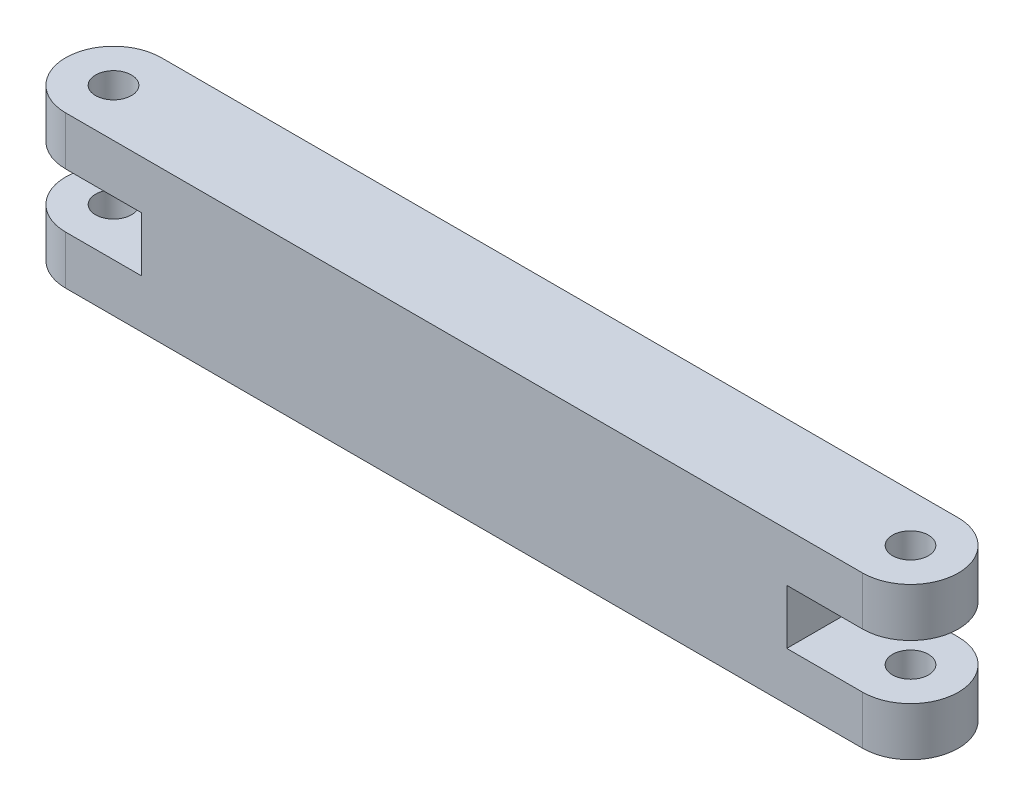
SolidWorks part; units mm, degrees
ref_plane "Front Plane" through (0, 0, 0) normal (0, 0, 1) x (1, 0, 0)
ref_plane "Top Plane" through (0, 0, 0) normal (0, 1, 0) x (1, 0, 0)
ref_plane "Right Plane" through (0, 0, 0) normal (1, 0, 0) x (0, 0, -1)
sketch "Sketch1" plane through (0, 0, 0) normal (0, 1, 0) x (1, 0, 0)
  line L0 (0, 0) -> (0, 17432.9303) construction
  line L1 (0, 0) -> (17432.9303, 0) construction
  line L2 (0, 6) -> (100, 6)
  line L3 (0, -6) -> (100, -6)
  circle A0 centre (0, 0) radius 2.25
  circle A1 centre (100, 0) radius 2.25
  arc A2 (0, 6) -> (0, -6) centre (0, 0) ccw
  arc A3 (100, -6) -> (100, 6) centre (100, 0) ccw
  dimension "D1" = 4.5
  dimension "D2" = 12
  dimension "D3" = 100
extrude "Boss-Extrude1" add sketch "Sketch1" along normal blind 19.05
sketch "Sketch2" plane through (0, 0, -6) normal (0, 0, -1) x (-1, 0, 0)
  line L0 (6.35, 9.525) -> (-49993.65, 9.525) construction
  line L1 (6, 0) -> (6, 19.05) construction
  line L2 (-50, 0) -> (-50, -50000) construction
  line L3 (-100, 0) -> (0, 0) construction
  line L5 (13.5, 6.096) -> (-113.5, 6.096) construction
  line L6 (13.5, 6.096) -> (13.5, 12.954) construction
  line L7 (13.5, 12.954) -> (-113.5, 12.954) construction
  line L8 (-113.5, 6.096) -> (-113.5, 12.954) construction
  line L9 (13.5, 6.096) -> (-113.5, 12.954) construction
  line L10 (13.5, 12.954) -> (-113.5, 6.096) construction
  line L11 (13.5, 12.954) -> (-9.525, 12.954)
  line L12 (13.5, 12.954) -> (13.5, 6.096)
  line L13 (13.5, 6.096) -> (-9.525, 6.096)
  line L14 (-9.525, 12.954) -> (-9.525, 6.096)
  point P4 (6, 9.525)
  point P9 (-50, 0)
  point P10 (-50, 9.525)
  dimension "D1" = 6.858
  dimension "D2" = 127
  dimension "D3" = 9.525
extrude "Cut-Extrude1" cut sketch "Sketch2" against normal blind 19.05
ref_axis "Axis1" through (50, 0, 6) along (0, 0, -1)
ref_plane "Plane1" through (50, 0, 0) normal (1, 0, 0) x (0, 0, -1)
mirror "Mirror1" about plane through (50, 0, 0) normal (1, 0, 0) of "Cut-Extrude1"
